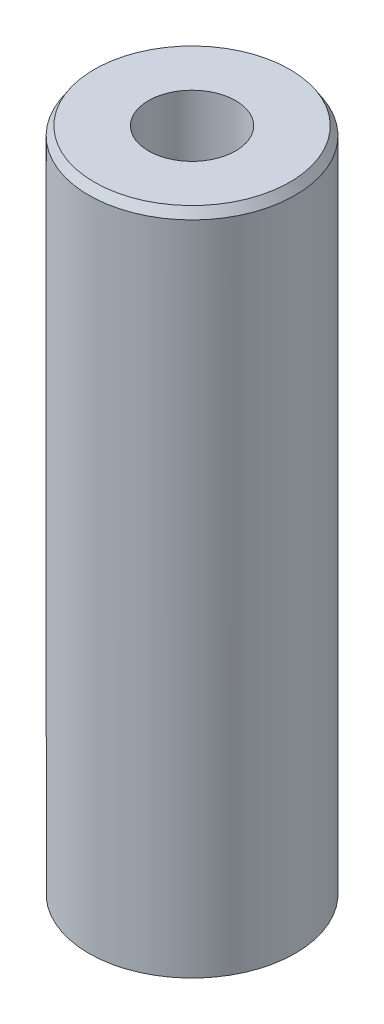
SolidWorks part; units mm, degrees
ref_plane "Front Plane" through (0, 0, 0) normal (0, 0, 1) x (1, 0, 0)
ref_plane "Top Plane" through (0, 0, 0) normal (0, 1, 0) x (1, 0, 0)
ref_plane "Right Plane" through (0, 0, 0) normal (1, 0, 0) x (0, 0, -1)
sketch "Sketch1" plane through (0, 0, 0) normal (0, 1, 0) x (1, 0, 0)
  circle A0 centre (0, 0) radius 7.5
  dimension "SHAFT_OD" = 15
extrude "Boss-Extrude1" add sketch "Sketch1" along normal blind 48.7329
sketch "Sketch2" plane through (0, 0, 0) normal (0, 1, 0) x (1, 0, 0)
  circle A0 centre (0, 0) radius 3.1692
  dimension "BORE_D" = 6.3384
extrude "Cut-Extrude1" cut sketch "Sketch2" along normal through all
chamfer "Chamfer1" distance 0.624 angle 32.493 2 edges at (0, 48.7329, 7.5) (0, 0, 7.5) first distance on face at (0, 48.7329, 7.5) first distance on face at (0, 0, 3.1692)
